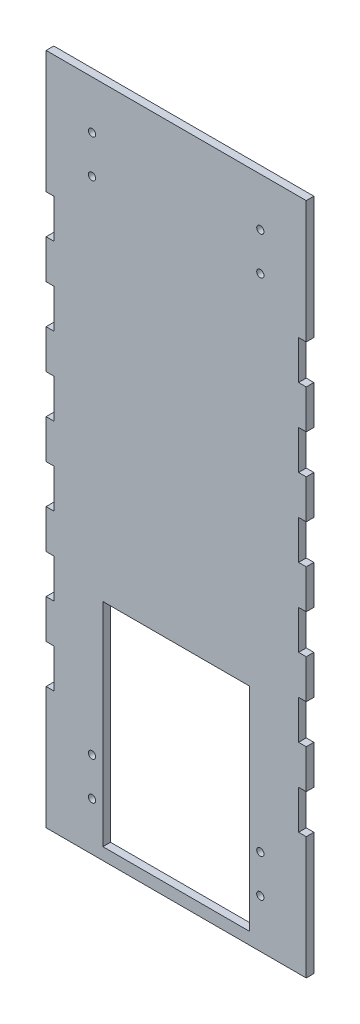
SolidWorks part; units mm, degrees
material "Acrylic (Medium-high impact)"
ref_plane "Front Plane" through (0, 0, 0) normal (0, 0, 1) x (1, 0, 0)
ref_plane "Top Plane" through (0, 0, 0) normal (0, 1, 0) x (1, 0, 0)
ref_plane "Right Plane" through (0, 0, 0) normal (1, 0, 0) x (0, 0, -1)
sketch "Sketch1" plane through (0, 0, 0) normal (0, 0, 1) x (1, 0, 0)
  line L5 (0, 279.4) -> (101.6, 279.4)
  line L87 (101.6, 0) -> (0, 0)
  line L88 (50.8, 279.4) -> (50.8, 0) construction
  line L89 (50.8, 139.7) -> (0, 139.7) construction
  line L90 (0, 0) -> (-3.175, 0)
  line L91 (-3.175, 0) -> (-3.175, 50.8)
  line L92 (-3.175, 50.8) -> (0, 50.8)
  line L93 (0, 50.8) -> (0, 0)
  line L94 (0, 228.6) -> (0, 279.4)
  line L95 (-3.175, 228.6) -> (0, 228.6)
  line L96 (-3.175, 279.4) -> (-3.175, 228.6)
  line L97 (0, 279.4) -> (-3.175, 279.4)
  line L98 (0, 50.8) -> (-3.175, 50.8)
  line L99 (-3.175, 50.8) -> (-3.175, 66.9636)
  line L100 (-3.175, 66.9636) -> (0, 66.9636)
  line L101 (0, 66.9636) -> (0, 50.8)
  line L102 (101.6, 228.6) -> (101.6, 279.4)
  line L103 (104.775, 228.6) -> (101.6, 228.6)
  line L104 (104.775, 279.4) -> (104.775, 228.6)
  line L105 (101.6, 279.4) -> (104.775, 279.4)
  line L106 (101.6, 66.9636) -> (101.6, 50.8)
  line L107 (104.775, 66.9636) -> (101.6, 66.9636)
  line L108 (104.775, 50.8) -> (104.775, 66.9636)
  line L109 (104.775, 50.8) -> (101.6, 50.8)
  line L110 (101.6, 50.8) -> (101.6, 0)
  line L111 (104.775, 0) -> (104.775, 50.8)
  line L112 (101.6, 0) -> (104.775, 0)
  line L113 (-3.175, 66.9636) -> (-3.175, 83.1273)
  line L114 (-3.175, 66.9636) -> (0, 66.9636)
  line L115 (0, 83.1273) -> (0, 66.9636)
  line L116 (-3.175, 83.1273) -> (0, 83.1273)
  line L117 (-3.175, 83.1273) -> (-3.175, 99.2909)
  line L118 (-3.175, 83.1273) -> (0, 83.1273)
  line L119 (0, 99.2909) -> (0, 83.1273)
  line L120 (-3.175, 99.2909) -> (0, 99.2909)
  line L121 (-3.175, 99.2909) -> (-3.175, 115.4545)
  line L122 (-3.175, 99.2909) -> (0, 99.2909)
  line L123 (0, 115.4545) -> (0, 99.2909)
  line L124 (-3.175, 115.4545) -> (0, 115.4545)
  line L125 (-3.175, 115.4545) -> (-3.175, 131.6182)
  line L126 (-3.175, 115.4545) -> (0, 115.4545)
  line L127 (0, 131.6182) -> (0, 115.4545)
  line L128 (-3.175, 131.6182) -> (0, 131.6182)
  line L129 (-3.175, 131.6182) -> (-3.175, 147.7818)
  line L130 (-3.175, 131.6182) -> (0, 131.6182)
  line L131 (0, 147.7818) -> (0, 131.6182)
  line L132 (-3.175, 147.7818) -> (0, 147.7818)
  line L133 (-3.175, 147.7818) -> (-3.175, 163.9455)
  line L134 (-3.175, 147.7818) -> (0, 147.7818)
  line L135 (0, 163.9455) -> (0, 147.7818)
  line L136 (-3.175, 163.9455) -> (0, 163.9455)
  line L137 (-3.175, 163.9455) -> (-3.175, 180.1091)
  line L138 (-3.175, 163.9455) -> (0, 163.9455)
  line L139 (0, 180.1091) -> (0, 163.9455)
  line L140 (-3.175, 180.1091) -> (0, 180.1091)
  line L141 (-3.175, 180.1091) -> (-3.175, 196.2727)
  line L142 (-3.175, 180.1091) -> (0, 180.1091)
  line L143 (0, 196.2727) -> (0, 180.1091)
  line L144 (-3.175, 196.2727) -> (0, 196.2727)
  line L145 (-3.175, 196.2727) -> (-3.175, 212.4364)
  line L146 (-3.175, 196.2727) -> (0, 196.2727)
  line L147 (0, 212.4364) -> (0, 196.2727)
  line L148 (-3.175, 212.4364) -> (0, 212.4364)
  line L149 (-3.175, 50.8) -> (-3.175, 66.9636) construction
  line L150 (0, 279.4) -> (0, 0)
  line L151 (104.775, 66.9636) -> (101.6, 66.9636)
  line L152 (101.6, 83.1273) -> (101.6, 66.9636)
  line L153 (104.775, 83.1273) -> (101.6, 83.1273)
  line L154 (104.775, 66.9636) -> (104.775, 83.1273)
  line L155 (104.775, 83.1273) -> (101.6, 83.1273)
  line L156 (101.6, 99.2909) -> (101.6, 83.1273)
  line L157 (104.775, 99.2909) -> (101.6, 99.2909)
  line L158 (104.775, 83.1273) -> (104.775, 99.2909)
  line L159 (104.775, 99.2909) -> (101.6, 99.2909)
  line L160 (101.6, 115.4545) -> (101.6, 99.2909)
  line L161 (104.775, 115.4545) -> (101.6, 115.4545)
  line L162 (104.775, 99.2909) -> (104.775, 115.4545)
  line L163 (104.775, 115.4545) -> (101.6, 115.4545)
  line L164 (101.6, 131.6182) -> (101.6, 115.4545)
  line L165 (104.775, 131.6182) -> (101.6, 131.6182)
  line L166 (104.775, 115.4545) -> (104.775, 131.6182)
  line L167 (104.775, 131.6182) -> (101.6, 131.6182)
  line L168 (101.6, 147.7818) -> (101.6, 131.6182)
  line L169 (104.775, 147.7818) -> (101.6, 147.7818)
  line L170 (104.775, 131.6182) -> (104.775, 147.7818)
  line L171 (104.775, 147.7818) -> (101.6, 147.7818)
  line L172 (101.6, 163.9455) -> (101.6, 147.7818)
  line L173 (104.775, 163.9455) -> (101.6, 163.9455)
  line L174 (104.775, 147.7818) -> (104.775, 163.9455)
  line L175 (104.775, 163.9455) -> (101.6, 163.9455)
  line L176 (101.6, 180.1091) -> (101.6, 163.9455)
  line L177 (104.775, 180.1091) -> (101.6, 180.1091)
  line L178 (104.775, 163.9455) -> (104.775, 180.1091)
  line L179 (104.775, 180.1091) -> (101.6, 180.1091)
  line L180 (101.6, 196.2727) -> (101.6, 180.1091)
  line L181 (104.775, 196.2727) -> (101.6, 196.2727)
  line L182 (104.775, 180.1091) -> (104.775, 196.2727)
  line L183 (104.775, 196.2727) -> (101.6, 196.2727)
  line L184 (101.6, 212.4364) -> (101.6, 196.2727)
  line L185 (104.775, 212.4364) -> (101.6, 212.4364)
  line L186 (104.775, 196.2727) -> (104.775, 212.4364)
  line L187 (104.775, 50.8) -> (104.775, 66.9636) construction
  line L188 (101.6, 279.4) -> (101.6, 50.8)
  line L189 (-3.175, 212.4364) -> (-3.175, 228.6)
  line L190 (-3.175, 212.4364) -> (0, 212.4364)
  line L191 (0, 228.6) -> (0, 212.4364)
  line L192 (-3.175, 228.6) -> (0, 228.6)
  line L193 (104.775, 212.4364) -> (101.6, 212.4364)
  line L194 (101.6, 228.6) -> (101.6, 212.4364)
  line L195 (104.775, 228.6) -> (101.6, 228.6)
  line L196 (104.775, 212.4364) -> (104.775, 228.6)
  dimension "D1" = 279.4
  dimension "D3" = 50.8
  dimension "D4" = 3.175
  dimension "D5" = 16.1636
  dimension "D7" = 16.1636
  dimension "D9" = 16.1636
  dimension "D2" = 101.6
  dimension "D6" = 11
  dimension "D8" = 11
extrude "Boss-Extrude1" add sketch "Sketch1" along normal blind 3.175 contours L188 L102 L5 L94 L150 L147 L143 L139 L135 L131 L127 L123 L119 L115 L101 L93 L87 L110 L106 L152 L156 L160 L164 L168 L172 L176 L180 L184 | L93 L92 L91 L90 | L116 L113 L100 L115 | L124 L121 L120 L123 | L132 L129 L128 L131 | L140 L137 L136 L139 | L148 L145 L144 L147 | L94 L97 L96 L95 | L105 L102 L103 L104 | L181 L186 L185 L184 | L173 L178 L177 L176 | L165 L170 L169 L168 | L157 L162 L161 L160 | L107 L154 L153 L152 | L110 L112 L111 L109
sketch "Sketch2" plane through (0, 0, 3.175) normal (0, 0, 1) x (1, 0, 0)
  line L0 (-3.175, 0) -> (-3.175, 50.8) construction
  line L1 (104.775, 0) -> (-3.175, 0) construction
  line L2 (50.8, 279.4) -> (50.8, 0) construction
  line L3 (-3.175, 279.4) -> (104.775, 279.4) construction
  line L4 (50.8, 139.7) -> (-3.175, 139.7) construction
  line L5 (-3.175, 131.6182) -> (-3.175, 147.7818) construction
  circle A0 centre (15.875, 20) radius 1.5
  circle A1 centre (15.875, 35.75) radius 1.5
  circle A2 centre (15.875, 243.65) radius 1.5
  circle A3 centre (15.875, 259.4) radius 1.5
  circle A4 centre (85.725, 259.4) radius 1.5
  circle A5 centre (85.725, 243.65) radius 1.5
  circle A6 centre (85.725, 35.75) radius 1.5
  circle A7 centre (85.725, 20) radius 1.5
  dimension "D1" = 3
  dimension "D2" = 3
  dimension "D3" = 15.75
  dimension "D4" = 19.05
  dimension "D5" = 20
extrude "Cut-Extrude1" cut sketch "Sketch2" against normal up to surface (3.175 mm away) up to face at (50.8, 139.7, 0)
sketch "Sketch3" plane through (0, 0, 3.175) normal (0, 0, 1) x (1, 0, 0)
  line L0 (20.375, 5) -> (20.375, 93.1333)
  line L1 (20.375, 93.1333) -> (81.225, 93.1333)
  line L2 (81.225, 93.1333) -> (81.225, 5)
  line L3 (81.225, 5) -> (20.375, 5)
  line L4 (104.775, 0) -> (-3.175, 0) construction
  line L5 (50.8, 279.4) -> (50.8, 0) construction
  line L6 (-3.175, 279.4) -> (104.775, 279.4) construction
  circle A0 centre (15.875, 20) radius 1.5 construction
  circle A1 centre (85.725, 20) radius 1.5 construction
  dimension "D1" = 5
  dimension "D2" = 4.5
  dimension "D3" = 4.5
  dimension "D4" = 279.4
  dimension "D5" = 93.1333
extrude "Cut-Extrude2" cut sketch "Sketch3" against normal up to surface (3.175 mm away) up to face at (17.375, 35.75, 0)
equation "\"D7@Sketch1\"=\"D5@Sketch1\""
equation "\"D5@Sketch1\"=((\"D1@Sketch1\"-2*\"D3@Sketch1\")/(\"D6@Sketch1\"))"
equation "\"D8@Sketch1\"=\"D6@Sketch1\""
equation "\"D9@Sketch1\"=\"D5@Sketch1\""
equation "\"D5@Sketch3\"=\"D4@Sketch3\"/3"
